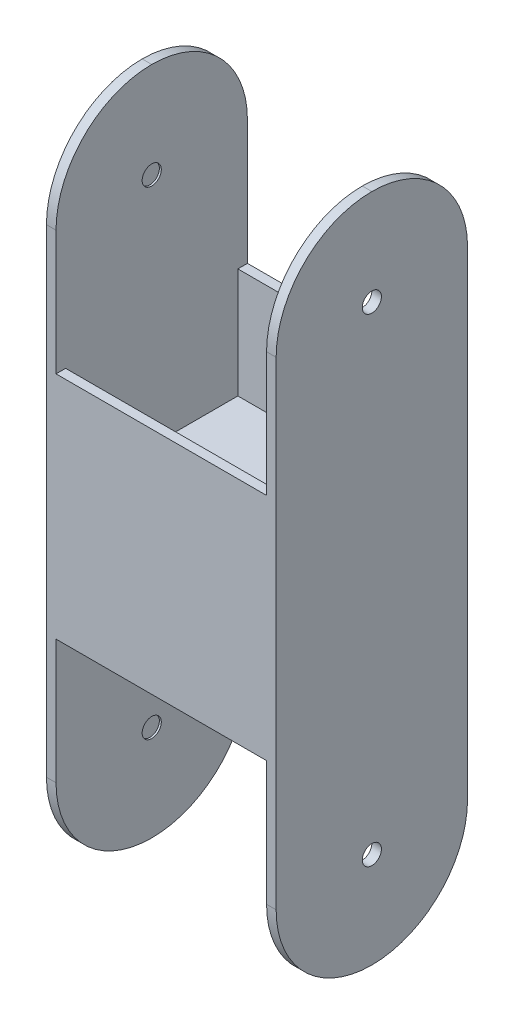
SolidWorks part; units mm, degrees
ref_plane "Front Plane" through (0, 0, 0) normal (0, 0, 1) x (1, 0, 0)
ref_plane "Top Plane" through (0, 0, 0) normal (0, 1, 0) x (1, 0, 0)
ref_plane "Right Plane" through (0, 0, 0) normal (1, 0, 0) x (0, 0, -1)
sketch "Sketch1" plane through (0, 0, 0) normal (0, 0, 1) x (1, 0, 0)
  line L0 (5, -8) -> (5, -172.5)
  line L1 (0, 0) -> (5, 0)
  line L2 (0, 0) -> (0, -350)
  line L3 (0, -350) -> (5, -350)
  line L4 (120, 0) -> (120, -350)
  line L5 (115, -9.5) -> (115, -172.5)
  line L6 (115, 0) -> (120, 0)
  line L7 (115, -350) -> (120, -350)
  line L8 (115, -177.5) -> (115, -293.5)
  line L9 (0, 0) -> (5, 0)
  line L10 (0, 0) -> (0, -8)
  line L12 (120, 0) -> (120, -9.5)
  line L13 (0, -350) -> (5, -350)
  line L14 (0, -350) -> (0, -292)
  line L16 (120, -350) -> (120, -293.5)
  line L17 (5, -172.5) -> (115, -172.5)
  line L18 (0, -146) -> (0, -154)
  line L19 (5, -177.5) -> (115, -177.5)
  line L20 (120, -147.5) -> (120, -155.5)
  line L21 (5, -177.5) -> (5, -292)
  line L22 (115, 0) -> (115, -9.5)
  line L23 (5, 0) -> (5, -8)
  line L24 (115, 0) -> (120, 0)
  line L25 (115, -350) -> (120, -350)
  line L26 (115, -293.5) -> (115, -350)
  line L27 (5, -292) -> (5, -350)
  dimension "D1" = 172.5
  dimension "D2" = 110
  dimension "D3" = 5
  dimension "D4" = 5
  dimension "D5" = 172.5
  dimension "D7" = 5
extrude "Boss-Extrude1" add sketch "Sketch1" along normal blind 100 contours L3 L13 L7 L4 L6 L9 L1 L2 L21 L19 L8 L17 L0 L5 region at (60, -175, 0)
fillet "Fillet1" radius 50 8 edges at (2.5, 0, 100) (2.5, 0, 0) (117.5, -350, 0) (117.5, -350, 100) (2.5, -350, 100) (2.5, -350, 0) (117.5, 0, 100) (117.5, 0, 0)
sketch "Sketch2" plane through (120, 0, 0) normal (1, 0, 0) x (0, 0, -1)
  circle A0 centre (-50, -300) radius 5
  circle A1 centre (-50, -50) radius 5
extrude "Cut-Extrude1" cut sketch "Sketch2" against normal blind 116
sketch "Sketch5" plane through (0, 0, 100) normal (0, 0, 1) x (1, 0, 0)
  line L12 (0, -50) -> (0, -300) construction
  line L13 (0, -115) -> (120, -115)
  line L14 (0, -115) -> (0, -235)
  line L15 (0, -235) -> (120, -235)
  line L16 (120, -115) -> (120, -235)
  line L17 (120, -50) -> (120, -300) construction
  line L18 (5, -50) -> (0, -50) construction
  dimension "D1" = 120
  dimension "D2" = 65
extrude "Boss-Extrude4" add sketch "Sketch5" against normal blind 5
sketch "Sketch6" plane through (0, 0, 0) normal (0, 0, -1) x (-1, 0, 0)
  line L9 (-115, -115) -> (-5, -115)
  line L10 (-115, -115) -> (-115, -235)
  line L11 (-115, -235) -> (-5, -235)
  line L12 (-5, -115) -> (-5, -235)
extrude "Boss-Extrude6" add sketch "Sketch6" against normal blind 5
